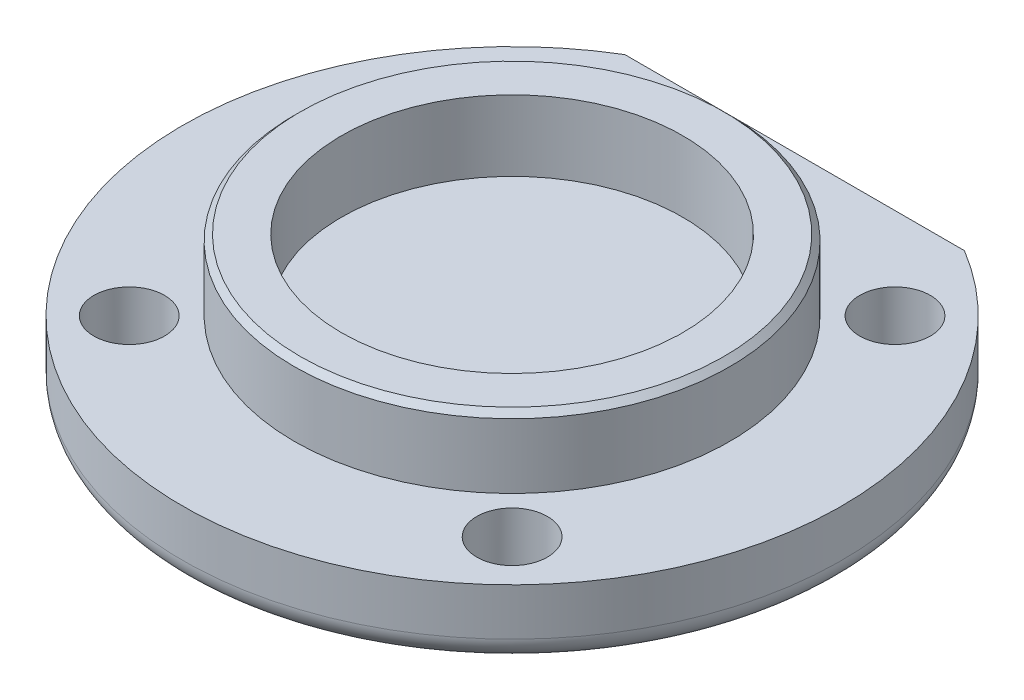
SolidWorks part; units mm, degrees
ref_plane "前视基准面" through (0, 0, 0) normal (0, 0, 1) x (1, 0, 0)
ref_plane "上视基准面" through (0, 0, 0) normal (0, 1, 0) x (1, 0, 0)
ref_plane "右视基准面" through (0, 0, 0) normal (1, 0, 0) x (0, 0, -1)
other "Configuration Table"
sketch "草图1" plane through (0, 0, 0) normal (0, 1, 0) x (1, 0, 0)
  line L0 (-14.4222, 24) -> (14.4222, 24)
  line L1 (0, 0) -> (-19.799, 19.799) construction
  arc A0 (-14.4222, 24) -> (14.4222, 24) centre (0, 0) ccw
  circle A1 centre (0, 0) radius 23 construction
  circle A2 centre (-16.2635, 16.2635) radius 3
  circle A3 centre (16.2635, 16.2635) radius 3
  circle A4 centre (16.2635, -16.2635) radius 3
  circle A5 centre (-16.2635, -16.2635) radius 3
  point P8 (16.5904, -16.5904)
  point P9 (16.2634, -16.2635)
  point P17 (0, 0)
  dimension "D1" = 56
  dimension "D2" = 46
  dimension "D5" = 6
  dimension "D3" = 24
  dimension "D4" = 45
  dimension "D6" = 4
extrude "凸台-拉伸1" add sketch "草图1" along normal blind 6
sketch "草图2" plane through (0, 6, 0) normal (0, 1, 0) x (1, 0, 0)
  circle A0 centre (0, 0) radius 18.5
  circle A1 centre (0, 0) radius 14.5
  dimension "D1" = 37
  dimension "D2" = 29
extrude "凸台-拉伸2" add sketch "草图2" along normal blind 6
fillet "圆角1" radius 2 1 edges at (0, 0, 28)
chamfer "倒角1" distance 0.5 angle 45 1 edges at (0, 12, 18.5)
